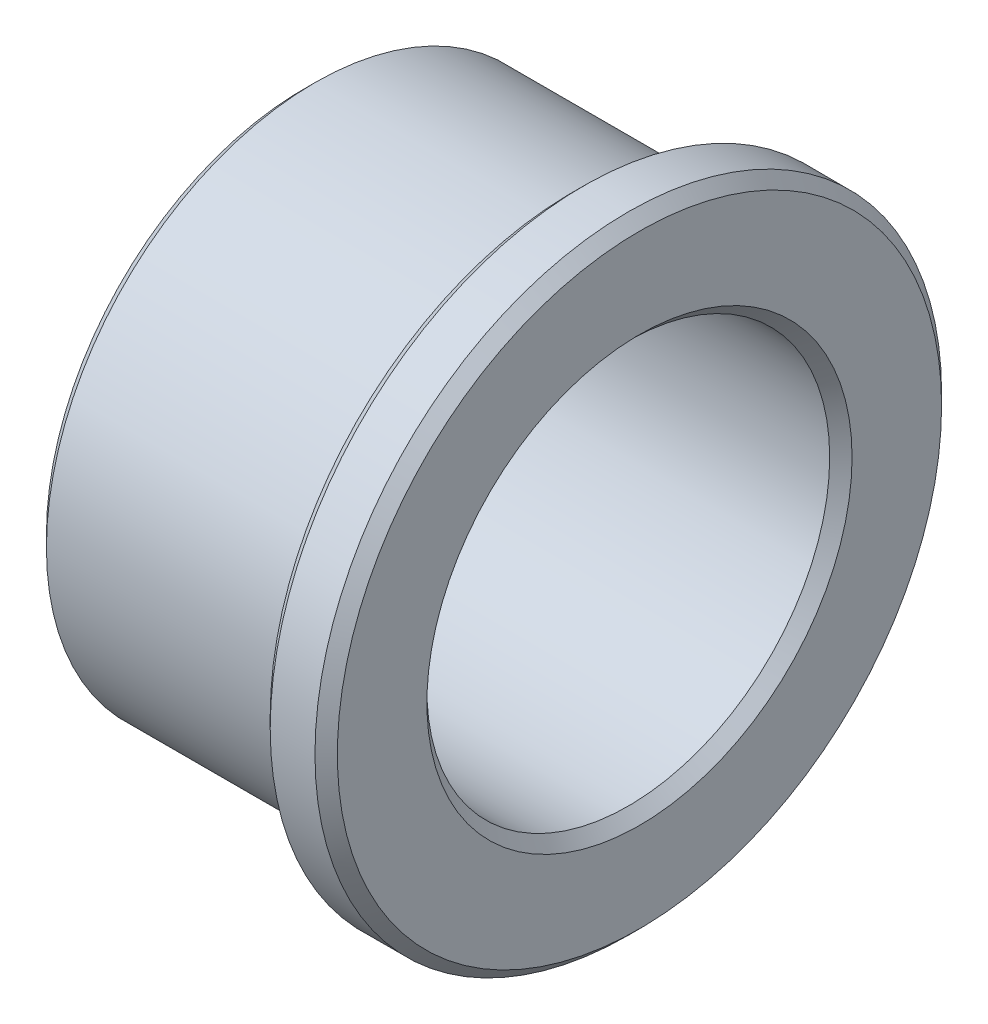
SolidWorks part; units mm, degrees
material "Tin Bearing Bronze"
ref_plane "Front Plane" through (0, 0, 0) normal (0, 0, 1) x (1, 0, 0)
ref_plane "Top Plane" through (0, 0, 0) normal (0, 1, 0) x (1, 0, 0)
ref_plane "Right Plane" through (0, 0, 0) normal (1, 0, 0) x (0, 0, -1)
sketch "Sketch1" plane through (0, 0, 0) normal (1, 0, 0) x (0, 0, -1)
  circle A0 centre (0, 0) radius 4.5
  circle A1 centre (0, 0) radius 7
  dimension "D1" = 9
  dimension "D2" = 14
extrude "Boss-Extrude1" add sketch "Sketch1" along normal blind 7.5
sketch "Sketch2" plane through (0, 0, 0) normal (-1, 0, 0) x (0, 0, 1)
  circle A0 centre (0, 0) radius 6
  dimension "D1" = 12
extrude "Cut-Extrude1" cut sketch "Sketch2" against normal blind 6 flip side to cut
chamfer "Chamfer1" distance 0.25 angle 45 5 edges at (0, 0, -4.5) (7.5, 0, -7) (7.5, 0, -4.5) (0, 0, 6) (6, 0, 7)
